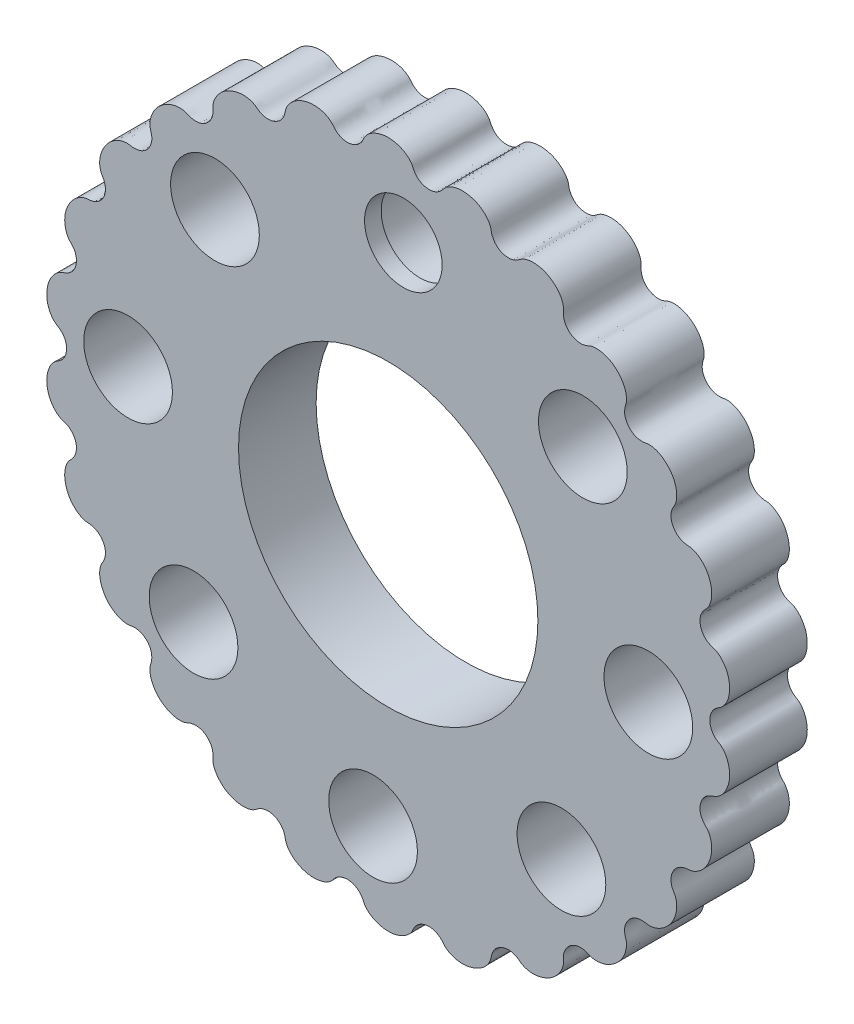
SolidWorks part; units mm, degrees
ref_plane "Front Plane" through (0, 0, 0) normal (0, 0, 1) x (1, 0, 0)
ref_plane "Top Plane" through (0, 0, 0) normal (0, 1, 0) x (1, 0, 0)
ref_plane "Right Plane" through (0, 0, 0) normal (1, 0, 0) x (0, 0, -1)
ref_plane "Plane1"
sketch "Sketch1" plane through (0, 0, 0) normal (0, 0, 1) x (1, 0, 0)
  circle A0 centre (23.4602, -1.3664) radius 4
  circle A1 centre (17.5551, 15.6227) radius 4
  circle A2 centre (1.3664, 23.4602) radius 4
  circle A3 centre (-15.6227, 17.5551) radius 4
  circle A4 centre (-23.4602, 1.3664) radius 4
  circle A5 centre (-17.5551, -15.6227) radius 4
  circle A6 centre (-1.3664, -23.4602) radius 4
  circle A7 centre (15.6227, -17.5551) radius 4
  circle A8 centre (0, 0) radius 13.5
  spline S0 degree 3 poles (29, 0) (29, -0.3768) (29.1535, -0.7032) (29.2804, -0.8839) (29.4951, -1.1897) (29.6235, -1.2426) (29.7, -1.2958) (29.8542, -1.4032) (29.8827, -1.413) (29.9346, -1.4485) (30.0574, -1.5322) (30.2266, -1.6673) (30.4081, -1.9555) (30.6633, -2.3609) (30.8614, -3.0668) (30.7707, -3.763) (30.6897, -4.3835) (30.3903, -4.9545) (30.0794, -5.2897) (29.8505, -5.5365) (29.6366, -5.6604) (29.4954, -5.7232) (29.4221, -5.7558) (29.3787, -5.7696) (29.2726, -5.805) (29.2187, -5.823) (29.1538, -5.8344) (28.9703, -5.9277) (28.8487, -5.9895) (28.6383, -6.0836) (28.4024, -6.4106) (28.2302, -6.6494) (28.1014, -7.0439) (28.114, -7.3663) (28.13, -7.7749) (28.2721, -8.0058) (28.3561, -8.139) (28.5057, -8.3761) (28.5682, -8.4123) (28.6126, -8.4587) (28.7112, -8.5615) (28.7444, -8.5938) (28.8088, -8.6819) (28.9486, -8.8731) (29.1514, -9.2784) (29.1753, -9.8433) (29.2016, -10.4629) (28.9684, -11.2228) (28.5673, -11.7445) (28.2242, -12.1907) (27.7962, -12.4491) (27.512, -12.5503) (27.3588, -12.6048) (27.2544, -12.621) (27.1583, -12.631) (27.0994, -12.6372) (27.0677, -12.6315) (26.8731, -12.6585) (26.7882, -12.6702) (26.6656, -12.6757) (26.4169, -12.7864) (26.2329, -12.8684) (25.9467, -13.0438) (25.7404, -13.3693) (25.5449, -13.678) (25.4898, -14.0569) (25.5065, -14.2975) (25.5338, -14.6901) (25.6313, -14.8203) (25.6773, -14.913) (25.7672, -15.0947) (25.7908, -15.1176) (25.819, -15.1687) (25.8858, -15.2896) (25.9587, -15.4408) (26.0003, -15.7215) (26.0635, -16.1484) (25.9783, -16.8383) (25.624, -17.4359) (25.2735, -18.0271) (24.6847, -18.475) (24.2049, -18.6519) (23.8505, -18.7825) (23.5839, -18.7865) (23.4237, -18.7723) (23.3532, -18.766) (23.3135, -18.758) (23.193, -18.7391) (23.1305, -18.7293) (23.0571, -18.7044) (22.817, -18.7127) (22.666, -18.718) (22.4117, -18.7282) (22.0741, -18.9277) (21.8037, -19.0874) (21.537, -19.4066) (21.4267, -19.6888) (21.2703, -20.0892) (21.3164, -20.3323) (21.3352, -20.4729) (21.3697, -20.7318) (21.4008, -20.775) (21.4173, -20.8314) (21.4554, -20.962) (21.476, -21.0337) (21.4871, -21.194) (21.5077, -21.4931) (21.432, -22.0351) (21.1005, -22.5638) (20.7525, -23.1188) (20.1283, -23.5982) (19.5445, -23.7905) (19.0833, -23.9425) (18.6768, -23.9306) (18.4374, -23.8827) (18.3183, -23.8589) (18.2417, -23.8315) (18.1648, -23.8002) (18.1153, -23.78) (18.0821, -23.7599) (17.9302, -23.7036) (17.8502, -23.674) (17.7421, -23.6178) (17.4519, -23.5986) (17.2532, -23.5854) (16.9238, -23.6055) (16.5911, -23.7932) (16.2828, -23.9672) (16.0549, -24.2657) (15.9532, -24.4853) (15.7864, -24.8455) (15.8095, -25.0146) (15.8061, -25.1217) (15.7995, -25.3288) (15.8106, -25.3619) (15.8121, -25.419) (15.8156, -25.554) (15.8124, -25.7044) (15.7327, -25.9537) (15.6076, -26.3448) (15.2434, -26.9124) (14.671, -27.2924) (14.1247, -27.6552) (13.4277, -27.8145) (12.9077, -27.7783) (12.4959, -27.7496) (12.2125, -27.6253) (12.0576, -27.5329) (11.9881, -27.4915) (11.9482, -27.4616) (11.8709, -27.4033) (11.8233, -27.3673) (11.7888, -27.3192) (11.5576, -27.1982) (11.4393, -27.1363) (11.2501, -27.0314) (10.8867, -27.0172) (10.599, -27.006) (10.2014, -27.1117) (9.9356, -27.3019) (9.6266, -27.5231) (9.5017, -27.7618) (9.4329, -27.9087) (9.301, -28.1902) (9.3096, -28.2703) (9.2956, -28.3375) (9.2644, -28.4872) (9.2586, -28.5276) (9.225, -28.6271) (9.1526, -28.842) (8.9513, -29.2246) (8.5213, -29.5648) (8.0513, -29.9367) (7.3217, -30.1953) (6.6665, -30.1855) (6.1495, -30.1778) (5.702, -30.0198) (5.428, -29.8555) (5.2317, -29.7378) (5.1254, -29.6318) (5.0489, -29.545) (5.0104, -29.5012) (4.9895, -29.4704) (4.8985, -29.3641) (4.8484, -29.3055) (4.797, -29.2149) (4.5489, -29.0464) (4.3992, -28.9447) (4.1364, -28.7982) (3.7557, -28.7793) (3.4144, -28.7624) (3.0427, -28.892) (2.8246, -29.0387) (2.4844, -29.2675) (2.4056, -29.4474) (2.3446, -29.5491) (2.2297, -29.7406) (2.2241, -29.781) (2.1999, -29.8314) (2.143, -29.9499) (2.0908, -30.0507) (1.9482, -30.2096) (1.7042, -30.4816) (1.1811, -30.8377) (0.5184, -30.9547) (-0.1433, -31.0716) (-0.8912, -30.9256) (-1.3839, -30.6514) (-1.7244, -30.4618) (-1.9423, -30.2342) (-2.0587, -30.0727) (-2.1328, -29.9699) (-2.1641, -29.907) (-2.2104, -29.8094) (-2.2297, -29.7686) (-2.2472, -29.7236) (-2.3086, -29.6118) (-2.354, -29.5292) (-2.4036, -29.3984) (-2.6485, -29.1765) (-2.8114, -29.029) (-3.1148, -28.8364) (-3.4891, -28.7894) (-3.8512, -28.7438) (-4.1885, -28.8477) (-4.3847, -28.9488) (-4.7171, -29.1199) (-4.7917, -29.2448) (-4.8562, -29.3161) (-4.9839, -29.457) (-4.9977, -29.4858) (-5.0369, -29.5312) (-5.1335, -29.6432) (-5.276, -29.7878) (-5.5725, -29.9342) (-5.9813, -30.1361) (-6.6691, -30.2631) (-7.3372, -30.1181) (-8.0054, -29.9731) (-8.5993, -29.5653) (-8.9067, -29.1864) (-9.1084, -28.9378) (-9.1972, -28.7228) (-9.2396, -28.5812) (-9.2583, -28.5188) (-9.2682, -28.4729) (-9.2832, -28.3986) (-9.2922, -28.3537) (-9.2988, -28.3029) (-9.3344, -28.1756) (-9.3615, -28.0789) (-9.3833, -27.9276) (-9.5864, -27.6486) (-9.7241, -27.4594) (-10.0027, -27.2036) (-10.3581, -27.0894) (-10.7123, -26.9756) (-11.0474, -27.018) (-11.2473, -27.0744) (-11.6072, -27.1758) (-11.6905, -27.2733) (-11.7631, -27.3241) (-11.9144, -27.4301) (-11.9326, -27.4513) (-11.9905, -27.4903) (-12.1265, -27.582) (-12.364, -27.7112) (-12.7623, -27.7637) (-13.2625, -27.8296) (-13.98, -27.7125) (-14.5617, -27.3617) (-15.1424, -27.0114) (-15.5442, -26.46) (-15.6987, -26.0512) (-15.796, -25.7936) (-15.8116, -25.6098) (-15.8127, -25.4806) (-15.8131, -25.431) (-15.8112, -25.3906) (-15.8081, -25.3148) (-15.806, -25.2642) (-15.7987, -25.2039) (-15.8099, -25.0483) (-15.8182, -24.933) (-15.8173, -24.7503) (-15.978, -24.4341) (-16.0929, -24.2081) (-16.344, -23.9163) (-16.6528, -23.7603) (-17.0099, -23.5797) (-17.3332, -23.5839) (-17.5212, -23.6047) (-17.8534, -23.6414) (-17.9327, -23.7033) (-18.0037, -23.7323) (-18.1561, -23.7944) (-18.1838, -23.8103) (-18.262, -23.8364) (-18.4404, -23.8958) (-18.7757, -23.9629) (-19.2368, -23.8716) (-19.7732, -23.7654) (-20.4268, -23.4061) (-20.8581, -22.8954) (-21.2862, -22.3886) (-21.4709, -21.7796) (-21.4889, -21.3946) (-21.5006, -21.1457) (-21.4689, -21.0138) (-21.4316, -20.881) (-21.4196, -20.8384) (-21.4053, -20.798) (-21.3781, -20.6911) (-21.3584, -20.6139) (-21.3146, -20.5126) (-21.3209, -20.2211) (-21.3252, -20.0275) (-21.3677, -19.6993) (-21.5965, -19.3708) (-21.805, -19.0713) (-22.1447, -18.8656) (-22.3836, -18.7883) (-22.7753, -18.6615) (-22.9389, -18.7099) (-23.0449, -18.72) (-23.2441, -18.739) (-23.2757, -18.7532) (-23.3323, -18.7614) (-23.4706, -18.7816) (-23.6339, -18.7969) (-23.9104, -18.7378) (-24.318, -18.6506) (-24.9112, -18.3483) (-25.344, -17.8314) (-25.7763, -17.3151) (-26.009, -16.6207) (-26.0223, -16.0997) (-26.0305, -15.7796) (-25.9715, -15.5311) (-25.9128, -15.3722) (-25.8794, -15.2821) (-25.8488, -15.2219) (-25.8135, -15.1588) (-25.7908, -15.1181) (-25.7677, -15.0833) (-25.7129, -14.9818) (-25.6787, -14.9186) (-25.6238, -14.8384) (-25.5603, -14.6098) (-25.5153, -14.4476) (-25.4561, -14.1735) (-25.552, -13.8037) (-25.6387, -13.4698) (-25.8918, -13.1306) (-26.1184, -12.9613) (-26.4466, -12.7161) (-26.6525, -12.6984) (-26.7739, -12.6749) (-26.9988, -12.6314) (-27.0428, -12.6411) (-27.0985, -12.6365) (-27.2342, -12.6254) (-27.3357, -12.6149) (-27.5268, -12.5449) (-27.8511, -12.4261) (-28.3537, -12.0954) (-28.7066, -11.5466) (-29.0604, -10.9965) (-29.2219, -10.2615) (-29.1644, -9.6901) (-29.1166, -9.2153) (-28.9463, -8.8757) (-28.8213, -8.6992) (-28.7612, -8.6144) (-28.7198, -8.5699) (-28.6508, -8.4983) (-28.6171, -8.4633) (-28.5778, -8.4304) (-28.4799, -8.3105) (-28.416, -8.2322) (-28.3073, -8.1242) (-28.1992, -7.8144) (-28.123, -7.5961) (-28.071, -7.229) (-28.1747, -6.8756) (-28.2827, -6.5076) (-28.5171, -6.2492) (-28.6801, -6.1162) (-28.9604, -5.8874) (-29.0858, -5.8722) (-29.1681, -5.8416) (-29.337, -5.7787) (-29.3662, -5.775) (-29.4289, -5.7508) (-29.5759, -5.6941) (-29.8003, -5.5836) (-30.0604, -5.31) (-30.3935, -4.9595) (-30.7169, -4.3332) (-30.7818, -3.6653) (-30.8458, -3.0063) (-30.656, -2.3551) (-30.4157, -1.9677) (-30.2771, -1.7444) (-30.1351, -1.6043) (-30.0301, -1.5193) (-29.9574, -1.4605) (-29.9166, -1.4356) (-29.8137, -1.3706) (-29.7667, -1.341) (-29.708, -1.3143) (-29.5579, -1.1868) (-29.4553, -1.0998) (-29.2724, -0.9632) (-29.1161, -0.5848) (-29.0009, -0.3057) (-28.9698, 0.1259) (-29.0654, 0.4425) (-29.1841, 0.8355) (-29.3773, 1.0194) (-29.4897, 1.1258) (-29.6904, 1.3157) (-29.7572, 1.3349) (-29.8106, 1.3687) (-29.9298, 1.444) (-29.9717, 1.4689) (-30.0584, 1.5428) (-30.2439, 1.701) (-30.5415, 2.06) (-30.6943, 2.6142) (-30.8613, 3.2202) (-30.8013, 4.0179) (-30.5269, 4.6132) (-30.2894, 5.1284) (-29.9282, 5.4693) (-29.6815, 5.6237) (-29.5751, 5.6903) (-29.4924, 5.7268) (-29.4191, 5.7546) (-29.3615, 5.7764) (-29.3277, 5.7831) (-29.1802, 5.8371) (-29.1098, 5.8629) (-29.0101, 5.8851) (-28.7932, 6.032) (-28.6486, 6.13) (-28.4211, 6.3101) (-28.2591, 6.6536) (-28.115, 6.959) (-28.0901, 7.3587) (-28.146, 7.6238) (-28.233, 8.0358) (-28.3787, 8.1814) (-28.4539, 8.278) (-28.5962, 8.4604) (-28.6326, 8.479) (-28.6715, 8.5199) (-28.763, 8.6159) (-28.8382, 8.6995) (-28.9365, 8.8892) (-29.1068, 9.218) (-29.2558, 9.8476) (-29.1217, 10.5193) (-28.9876, 11.1907) (-28.5674, 11.8414) (-28.1295, 12.1955) (-27.7806, 12.4777) (-27.461, 12.5803) (-27.2753, 12.6144) (-27.1996, 12.6284) (-27.1508, 12.6324) (-27.058, 12.6397) (-27.0015, 12.6441) (-26.9433, 12.6361) (-26.7233, 12.6854) (-26.6027, 12.7125) (-26.4096, 12.7473) (-26.1284, 12.9539) (-25.9109, 13.1136) (-25.6628, 13.4275) (-25.5663, 13.7523) (-25.453, 14.134) (-25.5114, 14.4283) (-25.5572, 14.5982) (-25.6376, 14.8968) (-25.7013, 14.962) (-25.7367, 15.0249) (-25.8126, 15.1598) (-25.8327, 15.1886) (-25.8686, 15.2659) (-25.9518, 15.4452) (-26.061, 15.7967) (-26.01, 16.2903) (-25.9515, 16.8559) (-25.6388, 17.5553) (-25.1623, 18.0295) (-24.7487, 18.441) (-24.2464, 18.6693) (-23.892, 18.7416) (-23.6537, 18.7902) (-23.494, 18.7817) (-23.375, 18.7672) (-23.3156, 18.7599) (-23.2803, 18.7506) (-23.1376, 18.7309) (-23.061, 18.7203) (-22.9621, 18.6866) (-22.6645, 18.7252) (-22.4847, 18.7486) (-22.1905, 18.8139) (-21.8935, 19.0526) (-21.627, 19.2669) (-21.4355, 19.6104) (-21.37, 19.8646) (-21.2676, 20.2613) (-21.328, 20.4476) (-21.3498, 20.564) (-21.3908, 20.7831) (-21.4134, 20.817) (-21.4287, 20.8708) (-21.4646, 20.9971) (-21.4925, 21.1077) (-21.4909, 21.322) (-21.4883, 21.6876) (-21.3324, 22.3006) (-20.9141, 22.8271) (-20.4969, 23.3522) (-19.8418, 23.7383) (-19.2919, 23.8601) (-18.9242, 23.9415) (-18.6172, 23.9206) (-18.4224, 23.8796) (-18.3156, 23.8572) (-18.2436, 23.8318) (-18.1736, 23.8037) (-18.1304, 23.7864) (-18.0938, 23.7688) (-17.9991, 23.7304) (-17.9282, 23.7016) (-17.8468, 23.6417) (-17.5259, 23.6052) (-17.3453, 23.5847) (-17.0425, 23.5774) (-16.6954, 23.7395) (-16.3857, 23.8842) (-16.1186, 24.1719) (-15.9945, 24.4026) (-15.8013, 24.7619) (-15.8149, 24.9569) (-15.8082, 25.075) (-15.7955, 25.2966) (-15.8092, 25.3354) (-15.8112, 25.3912) (-15.8159, 25.5219) (-15.8166, 25.6338) (-15.7656, 25.8382) (-15.6784, 26.1874) (-15.3894, 26.7385) (-14.8669, 27.1506) (-14.3457, 27.5617) (-13.6251, 27.7892) (-13.0592, 27.7842) (-12.6994, 27.7811) (-12.4096, 27.6997) (-12.223, 27.6178) (-12.089, 27.5589) (-12.0124, 27.5078) (-11.9354, 27.4515) (-11.8996, 27.4253) (-11.8677, 27.3989) (-11.7841, 27.339) (-11.7249, 27.2966) (-11.6545, 27.2288) (-11.4118, 27.1307) (-11.2514, 27.0658) (-10.9753, 26.9745) (-10.591, 27.0342) (-10.2451, 27.088) (-9.8867, 27.3072) (-9.6991, 27.511) (-9.423, 27.811) (-9.3864, 28.0067) (-9.3505, 28.1214) (-9.2836, 28.3352) (-9.2876, 28.3777) (-9.2763, 28.4322) (-9.2486, 28.5659) (-9.2229, 28.6754) (-9.1199, 28.868) (-8.9499, 29.1858) (-8.5383, 29.6467) (-7.9371, 29.9196) (-7.3363, 30.1923) (-6.5877, 30.2423) (-6.0406, 30.1047) (-5.6141, 29.9974) (-5.3226, 29.8039) (-5.1687, 29.6659) (-5.092, 29.5972) (-5.0504, 29.5488) (-4.993, 29.4787) (-4.9629, 29.4418) (-4.9364, 29.402) (-4.8378, 29.296) (-4.7759, 29.2295) (-4.6957, 29.124) (-4.4418, 28.9797) (-4.2603, 28.8765) (-3.9418, 28.7541) (-3.5679, 28.7815) (-3.1975, 28.8087) (-2.8689, 28.9896) (-2.691, 29.1394) (-2.3931, 29.3903) (-2.3498, 29.5357) (-2.3028, 29.6225) (-2.2089, 29.7958) (-2.2036, 29.8258) (-2.1759, 29.8802) (-2.1105, 30.0087) (-2.0098, 30.1776) (-1.7682, 30.3852) (-1.4156, 30.6881) (-0.7524, 30.9888) (-0.0462, 30.9996) (0.5923, 31.0095) (1.2195, 30.7852) (1.605, 30.5124) (1.8911, 30.3099) (2.0459, 30.1047) (2.1271, 29.9687) (2.1674, 29.9012) (2.1866, 29.8595) (2.233, 29.7615) (2.2574, 29.7101) (2.2757, 29.6475) (2.3926, 29.4734) (2.467, 29.3626) (2.5819, 29.1735) (2.9175, 28.9809) (3.168, 28.8371) (3.5705, 28.7467) (3.8942, 28.7925) (4.2967, 28.8494) (4.5186, 29.0167) (4.6452, 29.1172) (4.8699, 29.2955) (4.9004, 29.3654) (4.9422, 29.4163) (5.0342, 29.5284) (5.0599, 29.5628) (5.1339, 29.6337) (5.2974, 29.7904) (5.6534, 30.0364) (6.1935, 30.1383) (6.7871, 30.2502) (7.5608, 30.1369) (8.1381, 29.8188) (8.5814, 29.5746) (8.8978, 29.235) (9.0635, 28.9661) (9.1817, 28.7742) (9.2288, 28.6299) (9.2566, 28.5195) (9.2721, 28.4578) (9.2751, 28.4235) (9.3097, 28.2732) (9.3271, 28.1974) (9.3312, 28.0918) (9.4736, 27.8277) (9.5602, 27.6672) (9.7277, 27.415) (10.0569, 27.2235) (10.3531, 27.0512) (10.7416, 26.9964) (11.0012, 27.0259) (11.4075, 27.0722) (11.5587, 27.1944) (11.6592, 27.2559) (11.8484, 27.3716) (11.872, 27.4044) (11.9168, 27.4378) (12.0223, 27.5162) (12.1171, 27.5822) (12.32, 27.6568) (12.6643, 27.7836) (13.2928, 27.8533) (13.9323, 27.6481) (14.5689, 27.4437) (15.1594, 26.9699) (15.4677, 26.5005) (15.6598, 26.2079) (15.7515, 25.9314) (15.7876, 25.7371) (15.8135, 25.5976) (15.8146, 25.5084) (15.812, 25.4139) (15.8107, 25.37) (15.8071, 25.3286) (15.8054, 25.2261) (15.8042, 25.152) (15.7873, 25.0536) (15.8486, 24.7902) (15.8886, 24.6178) (15.9775, 24.3322) (16.2522, 24.0528) (16.5, 23.8009) (16.884, 23.6413) (17.1534, 23.6073) (17.5554, 23.5566) (17.7305, 23.6379) (17.8424, 23.6734) (18.0522, 23.7399) (18.0838, 23.7663) (18.1351, 23.7879) (18.2607, 23.8407) (18.372, 23.8837) (18.5979, 23.9067) (18.964, 23.9439) (19.5818, 23.8572) (20.1449, 23.51) (20.7265, 23.1512) (21.1918, 22.5303) (21.3724, 21.9933) (21.5123, 21.5773) (21.5021, 21.2423) (21.4707, 21.0529) (21.4559, 20.9637) (21.4417, 20.9149) (21.4113, 20.811) (21.396, 20.7587) (21.3706, 20.7041) (21.3403, 20.5085) (21.3217, 20.3886) (21.2811, 20.1993) (21.3727, 19.8542) (21.4432, 19.5887) (21.6547, 19.2307) (21.9337, 19.0214) (22.2541, 18.781) (22.5487, 18.735) (22.7224, 18.7188) (23.0278, 18.6903) (23.1091, 18.7262) (23.1795, 18.737) (23.3314, 18.7603) (23.3663, 18.7688) (23.4538, 18.7747) (23.6557, 18.7882) (24.0345, 18.7615) (24.4844, 18.5281) (24.9872, 18.2673) (25.5164, 17.7299) (25.7846, 17.1247) (26.0344, 16.5607) (26.0544, 15.9812) (25.984, 15.6272) (25.9382, 15.3975) (25.8769, 15.273) (25.8165, 15.1641) (25.7953, 15.126) (25.7738, 15.0918) (25.7285, 15.0103) (25.6952, 14.9504) (25.6409, 14.8794) (25.5698, 14.6426) (25.5237, 14.489) (25.4572, 14.2313) (25.5384, 13.8606) (25.6109, 13.53) (25.8522, 13.1716) (26.0831, 12.9885) (26.4073, 12.7314) (26.6245, 12.7057) (26.7511, 12.6794) (26.9837, 12.6313) (27.031, 12.6419) (27.0873, 12.6374) (27.2178, 12.627) (27.3027, 12.6189) (27.4671, 12.5656) (27.7686, 12.4677) (28.2609, 12.1788) (28.6308, 11.6587) (29.0015, 11.1375) (29.2039, 10.413) (29.1744, 9.8229) (29.1508, 9.3501) (29.0003, 8.9827) (28.873, 8.7772) (28.8085, 8.6732) (28.755, 8.6098) (28.6995, 8.5497) (28.6691, 8.5168) (28.6401, 8.4887) (28.5753, 8.4192) (28.5276, 8.3681) (28.4554, 8.3132) (28.3234, 8.0848) (28.2409, 7.9422) (28.1147, 7.6975) (28.1129, 7.3134) (28.1113, 6.9705) (28.2698, 6.5726) (28.4502, 6.3478) (28.708, 6.0265) (28.9074, 5.9561) (29.0214, 5.9028) (29.2318, 5.8044) (29.278, 5.8033) (29.3312, 5.7855) (29.4604, 5.7424) (29.552, 5.7099) (29.7161, 5.6015) (29.9966, 5.4162) (30.4023, 4.9904) (30.6205, 4.3846) (30.8435, 3.7652) (30.8343, 3.0004) (30.6428, 2.4484) (30.4865, 1.9983) (30.2416, 1.7041) (30.0764, 1.5584) (29.9937, 1.4856) (29.9406, 1.4506) (29.855, 1.3967) (29.8122, 1.3697) (29.766, 1.3487) (29.6294, 1.2444) (29.5505, 1.1842) (29.4269, 1.1035) (29.2607, 0.8551) (29.139, 0.6733) (29, 0.3574) (29, 0) (29, -0.3768) (29.1535, -0.7032) knots -0.259182 0 0 0 0.273271 0.273271 0.273271 0.73572 0.73572 0.73572 1.667811 1.667811 1.667811 3.867641 3.867641 3.867641 6.962071 6.962071 6.962071 9.72018 9.72018 9.72018 11.750932 11.750932 11.750932 12.805416 12.805416 12.805416 13.340183 13.340183 13.340183 13.694712 13.694712 13.694712 13.953634 13.953634 13.953634 14.281743 14.281743 14.281743 14.865962 14.865962 14.865962 16.163063 16.163063 16.163063 18.977016 18.977016 18.977016 22.06375 22.06375 22.06375 24.703877 24.703877 24.703877 26.127104 26.127104 26.127104 26.999377 26.999377 26.999377 27.380316 27.380316 27.380316 27.662164 27.662164 27.662164 27.929335 27.929335 27.929335 28.36543 28.36543 28.36543 29.219102 29.219102 29.219102 31.238876 31.238876 31.238876 34.311171 34.311171 34.311171 37.350654 37.350654 37.350654 39.595071 39.595071 39.595071 40.582862 40.582862 40.582862 41.095396 41.095396 41.095396 41.417912 41.417912 41.417912 41.676264 41.676264 41.676264 42.042748 42.042748 42.042748 42.717753 42.717753 42.717753 44.281405 44.281405 44.281405 47.199396 47.199396 47.199396 50.26224 50.26224 50.26224 52.682066 52.682066 52.682066 53.886048 53.886048 53.886048 54.662443 54.662443 54.662443 55.071214 55.071214 55.071214 55.351053 55.351053 55.351053 55.610487 55.610487 55.610487 56.036033 56.036033 56.036033 56.858516 56.858516 56.858516 58.803695 58.803695 58.803695 61.854553 61.854553 61.854553 64.766502 64.766502 64.766502 67.073013 67.073013 67.073013 68.107662 68.107662 68.107662 68.744786 68.744786 68.744786 69.071017 69.071017 69.071017 69.329235 69.329235 69.329235 69.62948 69.62948 69.62948 70.205013 70.205013 70.205013 71.488475 71.488475 71.488475 74.258794 74.258794 74.258794 77.286841 77.286841 77.286841 79.676527 79.676527 79.676527 81.388111 81.388111 81.388111 82.251079 82.251079 82.251079 82.726345 82.726345 82.726345 83.013148 83.013148 83.013148 83.270219 83.270219 83.270219 83.671043 83.671043 83.671043 84.425434 84.425434 84.425434 86.197564 86.197564 86.197564 89.229028 89.229028 89.229028 92.255429 92.255429 92.255429 94.347183 94.347183 94.347183 95.679653 95.679653 95.679653 96.236499 96.236499 96.236499 96.647911 96.647911 96.647911 96.921509 96.921509 96.921509 97.186211 97.186211 97.186211 97.634596 97.634596 97.634596 98.521506 98.521506 98.521506 100.708447 100.708447 100.708447 103.723018 103.723018 103.723018 106.738574 106.738574 106.738574 108.717179 108.717179 108.717179 109.589099 109.589099 109.589099 110.116095 110.116095 110.116095 110.516709 110.516709 110.516709 110.78834 110.78834 110.78834 111.059087 111.059087 111.059087 111.546664 111.546664 111.546664 112.56309 112.56309 112.56309 114.952876 114.952876 114.952876 117.954345 117.954345 117.954345 120.950868 120.950868 120.950868 122.839183 122.839183 122.839183 123.565209 123.565209 123.565209 124.049982 124.049982 124.049982 124.409254 124.409254 124.409254 124.666117 124.666117 124.666117 124.963231 124.963231 124.963231 125.488153 125.488153 125.488153 126.614587 126.614587 126.614587 129.185256 129.185256 129.185256 132.175578 132.175578 132.175578 135.143154 135.143154 135.143154 137.062298 137.062298 137.062298 137.678032 137.678032 137.678032 138.12276 138.12276 138.12276 138.41814 138.41814 138.41814 138.687346 138.687346 138.687346 139.128622 139.128622 139.128622 139.957815 139.957815 139.957815 141.985456 141.985456 141.985456 144.974918 144.974918 144.974918 147.960744 147.960744 147.960744 149.795195 149.795195 149.795195 150.835631 150.835631 150.835631 151.506978 151.506978 151.506978 151.924607 151.924607 151.924607 152.220913 152.220913 152.220913 152.488444 152.488444 152.488444 152.875803 152.875803 152.875803 153.593202 153.593202 153.593202 155.341578 155.341578 155.341578 158.308623 158.308623 158.308623 161.282783 161.282783 161.282783 163.754107 163.754107 163.754107 164.941245 164.941245 164.941245 165.522436 165.522436 165.522436 165.902275 165.902275 165.902275 166.170022 166.170022 166.170022 166.448877 166.448877 166.448877 166.928483 166.928483 166.928483 167.91343 167.91343 167.91343 170.22349 170.22349 170.22349 173.182408 173.182408 173.182408 176.101433 176.101433 176.101433 177.784641 177.784641 177.784641 178.949961 178.949961 178.949961 179.481526 179.481526 179.481526 179.844765 179.844765 179.844765 180.11262 180.11262 180.11262 180.44515 180.44515 180.44515 181.038587 181.038587 181.038587 182.362931 182.362931 182.362931 185.19794 185.19794 185.19794 188.297733 188.297733 188.297733 190.98058 190.98058 190.98058 192.137767 192.137767 192.137767 193.047282 193.047282 193.047282 193.481577 193.481577 193.481577 193.771277 193.771277 193.771277 194.028767 194.028767 194.028767 194.428899 194.428899 194.428899 195.185223 195.185223 195.185223 196.961489 196.961489 196.961489 200.040027 200.040027 200.040027 203.116656 203.116656 203.116656 205.567958 205.567958 205.567958 206.566423 206.566423 206.566423 207.174229 207.174229 207.174229 207.507609 207.507609 207.507609 207.765441 207.765441 207.765441 208.068419 208.068419 208.068419 208.600568 208.600568 208.600568 209.742311 209.742311 209.742311 212.39082 212.39082 212.39082 215.425744 215.425744 215.425744 218.059815 218.059815 218.059815 219.830399 219.830399 219.830399 220.714703 220.714703 220.714703 221.188761 221.188761 221.188761 221.475293 221.475293 221.475293 221.732377 221.732377 221.732377 222.133637 222.133637 222.133637 222.888965 222.888965 222.888965 224.663464 224.663464 224.663464 227.692233 227.692233 227.692233 230.71307 230.71307 230.71307 232.733178 232.733178 232.733178 233.840283 233.840283 233.840283 234.522989 234.522989 234.522989 235.034262 235.034262 235.034262 235.322087 235.322087 235.322087 235.578925 235.578925 235.578925 235.978901 235.978901 235.978901 236.729105 236.729105 236.729105 238.488881 238.488881 238.488881 241.493736 241.493736 241.493736 244.491666 244.491666 244.491666 246.39846 246.39846 246.39846 247.767079 247.767079 247.767079 248.403234 248.403234 248.403234 248.854331 248.854331 248.854331 249.152317 249.152317 249.152317 249.420576 249.420576 249.420576 249.815578 249.815578 249.815578 250.552381 250.552381 250.552381 252.35891 252.35891 252.35891 255.34034 255.34034 255.34034 258.319628 258.319628 258.319628 260.642143 260.642143 260.642143 261.798582 261.798582 261.798582 262.405476 262.405476 262.405476 262.786705 262.786705 262.786705 263.059324 263.059324 263.059324 263.329504 263.329504 263.329504 263.781667 263.781667 263.781667 264.684781 264.684781 264.684781 266.81857 266.81857 266.81857 269.932168 269.932168 269.932168 272.746787 272.746787 272.746787 274.835557 274.835557 274.835557 275.872957 275.872957 275.872957 276.417338 276.417338 276.417338 276.763895 276.763895 276.763895 277.022592 277.022592 277.022592 277.344291 277.344291 277.344291 277.915174 277.915174 277.915174 279.172481 279.172481 279.172481 281.949908 281.949908 281.949908 285.002315 285.002315 285.002315 287.345993 287.345993 287.345993 289.017912 289.017912 289.017912 289.951463 289.951463 289.951463 290.421965 290.421965 290.421965 290.707776 290.707776 290.707776 290.964901 290.964901 290.964901 291.367403 291.367403 291.367403 292.125519 292.125519 292.125519 293.907174 293.907174 293.907174 296.93058 296.93058 296.93058 299.940937 299.940937 299.940937 301.817782 301.817782 301.817782 303.165524 303.165524 303.165524 303.792603 303.792603 303.792603 304.246764 304.246764 304.246764 304.544214 304.544214 304.544214 304.812425 304.812425 304.812425 305.212705 305.212705 305.212705 305.962975 305.962975 305.962975 307.800356 307.800356 307.800356 310.778197 310.778197 310.778197 313.85456 313.85456 313.85456 316.2375 316.2375 316.2375 317.359832 317.359832 317.359832 317.924658 317.924658 317.924658 318.271121 318.271121 318.271121 318.537585 318.537585 318.537585 318.84351 318.84351 318.84351 319.381571 319.381571 319.381571 320.541854 320.541854 320.541854 323.218568 323.218568 323.218568 326.209995 326.209995 326.209995 328.997402 328.997402 328.997402 330.80632 330.80632 330.80632 331.438702 331.438702 331.438702 331.903936 331.903936 331.903936 332.205598 332.205598 332.205598 332.474634 332.474634 332.474634 332.852361 332.852361 332.852361 333.546306 333.546306 333.546306 335.153316 335.153316 335.153316 338.101884 338.101884 338.101884 341.056869 341.056869 341.056869 343.424761 343.424761 343.424761 344.622494 344.622494 344.622494 345.277713 345.277713 345.277713 345.759386 345.759386 345.759386 346.060354 346.060354 346.060354 346.329099 346.329099 346.329099 346.713058 346.713058 346.713058 347.421679 347.421679 347.421679 349.14232 349.14232 349.14232 352.084779 352.084779 352.084779 355.093551 355.093551 355.093551 357.546775 357.546775 357.546775 358.773388 358.773388 358.773388 359.386694 359.386694 359.386694 359.740818 359.740818 359.740818 360 360 360 360.273271 360.273271 360.273271 weights 1 1 1 1 1 1 1 1 1 1 1 1 1 1 1 1 1 1 1 1 1 1 1 1 1 1 1 1 1 1 1 1 1 1 1 1 1 1 1 1 1 1 1 1 1 1 1 1 1 1 1 1 1 1 1 1 1 1 1 1 1 1 1 1 1 1 1 1 1 1 1 1 1 1 1 1 1 1 1 1 1 1 1 1 1 1 1 1 1 1 1 1 1 1 1 1 1 1 1 1 1 1 1 1 1 1 1 1 1 1 1 1 1 1 1 1 1 1 1 1 1 1 1 1 1 1 1 1 1 1 1 1 1 1 1 1 1 1 1 1 1 1 1 1 1 1 1 1 1 1 1 1 1 1 1 1 1 1 1 1 1 1 1 1 1 1 1 1 1 1 1 1 1 1 1 1 1 1 1 1 1 1 1 1 1 1 1 1 1 1 1 1 1 1 1 1 1 1 1 1 1 1 1 1 1 1 1 1 1 1 1 1 1 1 1 1 1 1 1 1 1 1 1 1 1 1 1 1 1 1 1 1 1 1 1 1 1 1 1 1 1 1 1 1 1 1 1 1 1 1 1 1 1 1 1 1 1 1 1 1 1 1 1 1 1 1 1 1 1 1 1 1 1 1 1 1 1 1 1 1 1 1 1 1 1 1 1 1 1 1 1 1 1 1 1 1 1 1 1 1 1 1 1 1 1 1 1 1 1 1 1 1 1 1 1 1 1 1 1 1 1 1 1 1 1 1 1 1 1 1 1 1 1 1 1 1 1 1 1 1 1 1 1 1 1 1 1 1 1 1 1 1 1 1 1 1 1 1 1 1 1 1 1 1 1 1 1 1 1 1 1 1 1 1 1 1 1 1 1 1 1 1 1 1 1 1 1 1 1 1 1 1 1 1 1 1 1 1 1 1 1 1 1 1 1 1 1 1 1 1 1 1 1 1 1 1 1 1 1 1 1 1 1 1 1 1 1 1 1 1 1 1 1 1 1 1 1 1 1 1 1 1 1 1 1 1 1 1 1 1 1 1 1 1 1 1 1 1 1 1 1 1 1 1 1 1 1 1 1 1 1 1 1 1 1 1 1 1 1 1 1 1 1 1 1 1 1 1 1 1 1 1 1 1 1 1 1 1 1 1 1 1 1 1 1 1 1 1 1 1 1 1 1 1 1 1 1 1 1 1 1 1 1 1 1 1 1 1 1 1 1 1 1 1 1 1 1 1 1 1 1 1 1 1 1 1 1 1 1 1 1 1 1 1 1 1 1 1 1 1 1 1 1 1 1 1 1 1 1 1 1 1 1 1 1 1 1 1 1 1 1 1 1 1 1 1 1 1 1 1 1 1 1 1 1 1 1 1 1 1 1 1 1 1 1 1 1 1 1 1 1 1 1 1 1 1 1 1 1 1 1 1 1 1 1 1 1 1 1 1 1 1 1 1 1 1 1 1 1 1 1 1 1 1 1 1 1 1 1 1 1 1 1 1 1 1 1 1 1 1 1 1 1 1 1 1 1 1 1 1 1 1 1 1 1 1 1 1 1 1 1 1 1 1 1 1 1 1 1 1 1 1 1 1 1 1 1 1 1 1 1 1 1 1 1 1 1 1 1 1 1 1 1 1 1 1 1 1 1 1 1 1 1 1 1 1 1 1 1 1 1 1 1 1 1 1 1 1 1 1 1 1 1 1 1 1 1 1 1 1 1 1 1 1 1 1 1 1 1 1 1 1 1 1 1 1 1 1 1 1 1 1 1 1 1 1 1 1 1 1 1 1 1 1 1 1 1 1 1 1 1 1 1 1 1 1 1 1 1 1 1 1 1 1 1 1 1 1 1 1 1 1 1 1 1 1 1 1 1 1 1 1 1 1 1 1 1 1 1 1 1 1 1 1 1 1 1 only from (29, 0) to (29, 0)
extrude "Extrusion1" add sketch "Sketch1" along normal blind 7 contours S0 A8 A7 A6 A5 A4 A3 A2 A1 A0 region at (-28.1351, -0.0104, 0)
ref_plane "Plane2" through (0, 0, 7) normal (0, 0, 1) x (1, 0, 0)
sketch "Sketch2" plane through (0, 0, 7) normal (0, 0, 1) x (1, 0, 0)
  circle A0 centre (1.3664, 23.4602) radius 4
  circle A1 centre (1.3664, 23.4602) radius 3.5
extrude "Extrusion2" add sketch "Sketch2" against normal blind 1.5 contours A0 A1 region at (-2.5205, 23.4602, 7)
ref_plane "Plane3" through (0, 0, 0) normal (-1, 0, 0) x (0, 0, 1)
ref_plane "Plane4" through (0, 0, 0) normal (0, -1, 0) x (0, 0, 1)
ref_axis "Axis1" through (0, 0, 80.9) along (0, 0, -1)
pattern_circular "CirPattern1" count 8 every 45 about axis through (0, 0, 80.9) along (0, 0, -1) rebuild error yes
